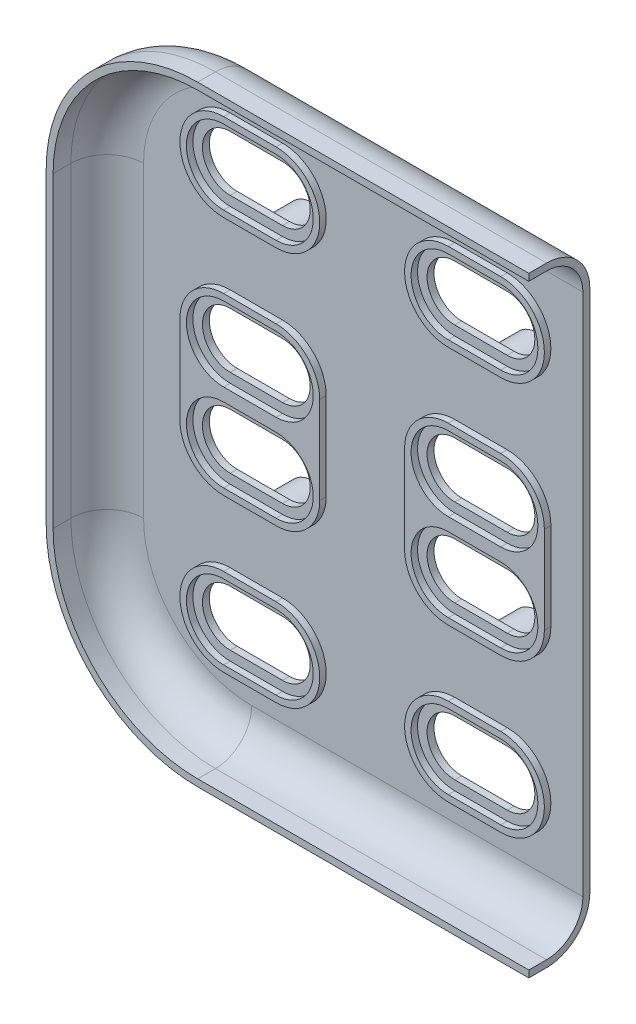
SolidWorks part; units mm, degrees
ref_plane "Front Plane" through (0, 0, 0) normal (0, 0, 1) x (1, 0, 0)
ref_plane "Top Plane" through (0, 0, 0) normal (0, 1, 0) x (1, 0, 0)
ref_plane "Right Plane" through (0, 0, 0) normal (1, 0, 0) x (0, 0, -1)
sketch "Sketch1" plane through (0, 0, 0) normal (0, 0, 1) x (1, 0, 0)
  line L1 (-15.748, 16.51) -> (15.748, 16.51)
  line L2 (-15.748, 16.51) -> (-15.748, -16.51)
  line L3 (-15.748, -16.51) -> (15.748, -16.51)
  line L4 (15.748, 16.51) -> (15.748, -16.51)
  dimension "D1" = 31.496
  dimension "D2" = 15.748
  dimension "D3" = 33.02
  dimension "D4" = 16.51
extrude "Boss-Extrude1" add sketch "Sketch1" along normal blind 6.9088
shell "Shell1" thickness 0.3048 removed face at (0, 16.51, 3.4544)
sketch "Sketch2" plane through (0, 0, 0) normal (1, 0, 0) x (0, 0, -1)
  line L0 (-6.9088, 16.51) -> (0, 16.51) construction
  line L1 (-3.4544, 16.51) -> (0.4052, 16.51)
  line L2 (-3.4544, 16.51) -> (-3.4544, -16.733)
  line L3 (-3.4544, -16.733) -> (0.4052, -16.733)
  line L4 (0.4052, 16.51) -> (0.4052, -16.733)
extrude "Cut-Extrude1" cut sketch "Sketch2" against normal mid plane 34.5948
sketch "Sketch3" plane through (0, 0, 6.9088) normal (0, 0, 1) x (1, 0, 0)
  line L0 (-8.128, 12.954) -> (-5.0546, 12.954) construction
  line L1 (-8.128, 14.5796) -> (-5.0546, 14.5796)
  line L2 (-8.128, 11.3284) -> (-5.0546, 11.3284)
  line L3 (-15.748, -6.985) -> (-15.748, 16.51) construction
  line L4 (15.748, 16.51) -> (-15.748, 16.51) construction
  arc A0 (-8.128, 14.5796) -> (-8.128, 11.3284) centre (-8.128, 12.954) ccw
  arc A1 (-5.0546, 11.3284) -> (-5.0546, 14.5796) centre (-5.0546, 12.954) ccw
  point P2 (-6.5913, 12.954)
  dimension "D1" = 1.6256
  dimension "D2" = 3.0734
  dimension "D3" = 7.62
  dimension "D4" = 3.556
extrude "Cut-Extrude2" cut sketch "Sketch3" against normal through all
sketch "Sketch4" plane through (0, 0, 6.9088) normal (0, 0, 1) x (1, 0, 0)
  line L0 (-15.748, -6.985) -> (-15.748, 16.51) construction
  circle A0 centre (-6.6167, 8.4582) radius 1.143
  arc A1 (-5.0546, 11.3284) -> (-5.0546, 14.5796) centre (-5.0546, 12.954) ccw construction
  dimension "D1" = 2.286
  dimension "D2" = 4.4958
  dimension "D3" = 9.1313
extrude "Cut-Extrude3" cut sketch "Sketch4" against normal through all
sketch "Sketch5" plane through (0, 0, 6.9088) normal (0, 0, 1) x (1, 0, 0)
  line L0 (-8.128, 3.9624) -> (-5.0546, 3.9624) construction
  line L1 (-8.128, 5.588) -> (-5.0546, 5.588)
  line L2 (-8.128, 2.3368) -> (-5.0546, 2.3368)
  line L3 (-8.128, -1.1684) -> (-5.0546, -1.1684) construction
  line L4 (-8.128, 0.4572) -> (-5.0546, 0.4572)
  line L5 (-8.128, -2.794) -> (-5.0546, -2.794)
  line L6 (-15.748, -6.985) -> (-15.748, 16.51) construction
  line L7 (-8.128, -10.16) -> (-5.0546, -10.16) construction
  line L8 (-8.128, -8.5344) -> (-5.0546, -8.5344)
  line L9 (-8.128, -11.7856) -> (-5.0546, -11.7856)
  arc A0 (-8.128, 5.588) -> (-8.128, 2.3368) centre (-8.128, 3.9624) ccw
  arc A1 (-5.0546, 2.3368) -> (-5.0546, 5.588) centre (-5.0546, 3.9624) ccw
  arc A2 (-8.128, 0.4572) -> (-8.128, -2.794) centre (-8.128, -1.1684) ccw
  arc A3 (-5.0546, -2.794) -> (-5.0546, 0.4572) centre (-5.0546, -1.1684) ccw
  circle A4 centre (-6.6167, 8.4582) radius 1.143 construction
  circle A5 centre (-6.5913, -5.6642) radius 1.143
  arc A6 (-8.128, -8.5344) -> (-8.128, -11.7856) centre (-8.128, -10.16) ccw
  arc A7 (-5.0546, -11.7856) -> (-5.0546, -8.5344) centre (-5.0546, -10.16) ccw
  point P2 (-6.5913, 3.9624)
  point P7 (-6.5913, -1.1684)
  point P22 (-6.5913, -10.16)
  dimension "D1" = 1.6256
  dimension "D2" = 1.6256
  dimension "D4" = 3.0734
  dimension "D9" = 2.286
  dimension "D11" = 1.6256
  dimension "D3" = 4.4958
  dimension "D5" = 3.0734
  dimension "D6" = 5.1308
  dimension "D7" = 7.62
  dimension "D8" = 7.62
  dimension "D10" = 4.4958
  dimension "D12" = 8.9916
  dimension "D13" = 7.62
  dimension "D14" = 3.0734
extrude "Cut-Extrude4" cut sketch "Sketch5" against normal blind 2.54
mirror "Mirror1" about plane through (0, 0, 0) normal (1, 0, 0) of "Cut-Extrude4", "Cut-Extrude3", "Cut-Extrude2"
sketch "Sketch6" plane through (0, 0, 3.4544) normal (0, 0, -1) x (-1, 0, 0)
  line L1 (-15.748, -16.51) -> (15.748, -16.51)
  line L2 (-15.748, -16.51) -> (-15.748, 16.51)
  line L3 (-15.748, 16.51) -> (15.748, 16.51)
  line L4 (15.748, -16.51) -> (15.748, 16.51)
extrude "Cut-Extrude5" cut sketch "Sketch6" against normal up to surface (3.1496 mm away) up to face at (6.5913, -1.1684, 6.604)
sketch "Sketch7" plane through (0, 0, 6.604) normal (0, 0, -1) x (-1, 0, 0)
  line L1 (-15.748, 16.51) -> (15.748, 16.51)
  line L2 (-15.748, 16.51) -> (-15.748, 19.304)
  line L3 (-15.748, 19.304) -> (15.748, 19.304)
  line L4 (15.748, 16.51) -> (15.748, 19.304)
  dimension "D1" = 2.794
extrude "Boss-Extrude2" add sketch "Sketch7" against normal up to surface (0.3048 mm away) up to face at (6.5913, -10.16, 6.9088)
fillet "Fillet1" radius 8.89 2 edges at (-15.748, -16.51, 6.7564) (-15.748, 19.304, 6.7564)
sketch "Sketch9" plane through (0, 0, 6.9088) normal (0, 0, 1) x (1, 0, 0)
  line L0 (-6.858, -16.51) -> (15.748, -16.51) construction
  line L1 (-15.748, 10.414) -> (-15.748, -7.62) construction
  line L2 (-6.858, 19.304) -> (15.748, 19.304) construction
  line L3 (15.748, -16.51) -> (15.748, 19.304) construction
  line L4 (-6.858, -16.51) -> (15.748, -16.51)
  line L5 (-15.748, 10.414) -> (-15.748, -7.62)
  line L6 (-6.858, 19.304) -> (15.748, 19.304)
  line L7 (15.748, -16.51) -> (15.748, 19.304)
  arc A0 (-15.748, -7.62) -> (-6.858, -16.51) centre (-6.858, -7.62) ccw construction
  arc A1 (-6.858, 19.304) -> (-15.748, 10.414) centre (-6.858, 10.414) ccw construction
  arc A2 (-15.748, -7.62) -> (-6.858, -16.51) centre (-6.858, -7.62) ccw
  arc A3 (-6.858, 19.304) -> (-15.748, 10.414) centre (-6.858, 10.414) ccw
extrude "Boss-Extrude4" add sketch "Sketch9" along normal blind 3.0226
fillet "Fillet2" radius 2.54 5 edges at (4.445, -16.51, 6.604) (-13.1442, -13.9062, 6.604) (-15.748, 1.397, 6.604) (-13.1442, 16.7002, 6.604) (4.445, 19.304, 6.604)
shell "Shell3" thickness 0.4064 removed face at (-2.8997, 1.397, 9.9314)
sketch "Sketch10" plane through (15.3416, 0, 0) normal (-1, 0, 0) x (0, 0, 1)
  line L0 (9.9314, 18.8976) -> (9.144, 18.8976) construction
  line L1 (9.9314, -16.1036) -> (9.9314, 18.8976) construction
  line L2 (9.9314, -16.1036) -> (9.144, -16.1036) construction
  line L3 (7.0104, 16.764) -> (7.0104, -13.97) construction
  line L4 (9.9314, 18.8976) -> (9.144, 18.8976)
  line L5 (9.9314, -16.1036) -> (9.9314, 18.8976)
  line L6 (9.9314, -16.1036) -> (9.144, -16.1036)
  line L7 (7.0104, 16.764) -> (7.0104, -13.97)
  arc A0 (7.0104, -13.97) -> (9.144, -16.1036) centre (9.144, -13.97) ccw construction
  arc A1 (9.144, 18.8976) -> (7.0104, 16.764) centre (9.144, 16.764) ccw construction
  arc A2 (7.0104, -13.97) -> (9.144, -16.1036) centre (9.144, -13.97) ccw
  arc A3 (9.144, 18.8976) -> (7.0104, 16.764) centre (9.144, 16.764) ccw
extrude "Cut-Extrude6" cut sketch "Sketch10" against normal blind 3.0226
sketch "Sketch12" plane through (0, 0, 6.604) normal (0, 0, -1) x (-1, 0, 0)
  line L0 (-8.128, -11.7856) -> (-5.0546, -11.7856) construction
  line L1 (-5.0546, -8.5344) -> (-8.128, -8.5344) construction
  line L2 (-8.128, -2.794) -> (-5.0546, -2.794) construction
  line L3 (-5.0546, 0.4572) -> (-8.128, 0.4572) construction
  line L4 (-8.128, 2.3368) -> (-5.0546, 2.3368) construction
  line L5 (-5.0546, 5.588) -> (-8.128, 5.588) construction
  line L6 (-8.128, 11.3284) -> (-5.0546, 11.3284) construction
  line L7 (-5.0546, 14.5796) -> (-8.128, 14.5796) construction
  line L8 (-8.128, -11.7856) -> (-5.0546, -11.7856)
  line L9 (-5.0546, -8.5344) -> (-8.128, -8.5344)
  line L10 (-8.128, -2.794) -> (-5.0546, -2.794)
  line L11 (-5.0546, 0.4572) -> (-8.128, 0.4572)
  line L12 (-8.128, 2.3368) -> (-5.0546, 2.3368)
  line L13 (-5.0546, 5.588) -> (-8.128, 5.588)
  line L14 (-8.128, 11.3284) -> (-5.0546, 11.3284)
  line L15 (-5.0546, 14.5796) -> (-8.128, 14.5796)
  arc A0 (-8.128, -8.5344) -> (-8.128, -11.7856) centre (-8.128, -10.16) ccw construction
  arc A1 (-5.0546, -11.7856) -> (-5.0546, -8.5344) centre (-5.0546, -10.16) ccw construction
  circle A2 centre (-6.5913, -5.6642) radius 1.143 construction
  arc A3 (-8.128, 0.4572) -> (-8.128, -2.794) centre (-8.128, -1.1684) ccw construction
  arc A4 (-5.0546, -2.794) -> (-5.0546, 0.4572) centre (-5.0546, -1.1684) ccw construction
  arc A5 (-8.128, 5.588) -> (-8.128, 2.3368) centre (-8.128, 3.9624) ccw construction
  arc A6 (-5.0546, 2.3368) -> (-5.0546, 5.588) centre (-5.0546, 3.9624) ccw construction
  circle A7 centre (-6.6167, 8.4582) radius 1.143 construction
  arc A8 (-8.128, 14.5796) -> (-8.128, 11.3284) centre (-8.128, 12.954) ccw construction
  arc A9 (-5.0546, 11.3284) -> (-5.0546, 14.5796) centre (-5.0546, 12.954) ccw construction
  arc A10 (-8.128, -8.5344) -> (-8.128, -11.7856) centre (-8.128, -10.16) ccw
  arc A11 (-5.0546, -11.7856) -> (-5.0546, -8.5344) centre (-5.0546, -10.16) ccw
  circle A12 centre (-6.5913, -5.6642) radius 1.143
  arc A13 (-8.128, 0.4572) -> (-8.128, -2.794) centre (-8.128, -1.1684) ccw
  arc A14 (-5.0546, -2.794) -> (-5.0546, 0.4572) centre (-5.0546, -1.1684) ccw
  arc A15 (-8.128, 5.588) -> (-8.128, 2.3368) centre (-8.128, 3.9624) ccw
  arc A16 (-5.0546, 2.3368) -> (-5.0546, 5.588) centre (-5.0546, 3.9624) ccw
  circle A17 centre (-6.6167, 8.4582) radius 1.143
  arc A18 (-8.128, 14.5796) -> (-8.128, 11.3284) centre (-8.128, 12.954) ccw
  arc A19 (-5.0546, 11.3284) -> (-5.0546, 14.5796) centre (-5.0546, 12.954) ccw
extrude "Cut-Extrude7" cut sketch "Sketch12" against normal blind 3.0226
mirror "Mirror2" about plane through (0, 0, 0) normal (1, 0, 0) of "Mirror1"
sketch "Sketch14" plane through (0, 0, 6.604) normal (0, 0, -1) x (-1, 0, 0)
  line L0 (5.0546, 14.5796) -> (8.128, 14.5796) construction
  line L1 (8.128, 11.3284) -> (5.0546, 11.3284) construction
  line L2 (5.0546, 5.588) -> (8.128, 5.588) construction
  line L3 (8.128, 2.3368) -> (5.0546, 2.3368) construction
  line L4 (5.0546, 0.4572) -> (8.128, 0.4572) construction
  line L5 (8.128, -2.794) -> (5.0546, -2.794) construction
  line L6 (8.128, -11.7856) -> (5.0546, -11.7856) construction
  line L7 (5.0546, -8.5344) -> (8.128, -8.5344) construction
  line L8 (5.0546, 14.5796) -> (8.128, 14.5796)
  line L9 (8.128, 11.3284) -> (5.0546, 11.3284)
  line L10 (5.0546, 5.588) -> (8.128, 5.588)
  line L11 (8.128, 2.3368) -> (5.0546, 2.3368)
  line L12 (5.0546, 0.4572) -> (8.128, 0.4572)
  line L13 (8.128, -2.794) -> (5.0546, -2.794)
  line L14 (8.128, -11.7856) -> (5.0546, -11.7856)
  line L15 (5.0546, -8.5344) -> (8.128, -8.5344)
  arc A0 (8.128, 11.3284) -> (8.128, 14.5796) centre (8.128, 12.954) ccw construction
  arc A1 (5.0546, 14.5796) -> (5.0546, 11.3284) centre (5.0546, 12.954) ccw construction
  circle A2 centre (6.6167, 8.4582) radius 1.143 construction
  arc A3 (8.128, 2.3368) -> (8.128, 5.588) centre (8.128, 3.9624) ccw construction
  arc A4 (5.0546, 5.588) -> (5.0546, 2.3368) centre (5.0546, 3.9624) ccw construction
  arc A5 (8.128, -2.794) -> (8.128, 0.4572) centre (8.128, -1.1684) ccw construction
  arc A6 (5.0546, 0.4572) -> (5.0546, -2.794) centre (5.0546, -1.1684) ccw construction
  circle A7 centre (6.5913, -5.6642) radius 1.143 construction
  arc A8 (8.128, -11.7856) -> (8.128, -8.5344) centre (8.128, -10.16) ccw construction
  arc A9 (5.0546, -8.5344) -> (5.0546, -11.7856) centre (5.0546, -10.16) ccw construction
  arc A10 (8.128, 11.3284) -> (8.128, 14.5796) centre (8.128, 12.954) ccw
  arc A11 (5.0546, 14.5796) -> (5.0546, 11.3284) centre (5.0546, 12.954) ccw
  circle A12 centre (6.6167, 8.4582) radius 1.143
  arc A13 (8.128, 2.3368) -> (8.128, 5.588) centre (8.128, 3.9624) ccw
  arc A14 (5.0546, 5.588) -> (5.0546, 2.3368) centre (5.0546, 3.9624) ccw
  arc A15 (8.128, -2.794) -> (8.128, 0.4572) centre (8.128, -1.1684) ccw
  arc A16 (5.0546, 0.4572) -> (5.0546, -2.794) centre (5.0546, -1.1684) ccw
  circle A17 centre (6.5913, -5.6642) radius 1.143
  arc A18 (8.128, -11.7856) -> (8.128, -8.5344) centre (8.128, -10.16) ccw
  arc A19 (5.0546, -8.5344) -> (5.0546, -11.7856) centre (5.0546, -10.16) ccw
extrude "Cut-Extrude8" cut sketch "Sketch14" against normal blind 3.0226
sketch "Sketch15" plane through (0, 0, 7.3152) normal (0, 0, 1) x (1, 0, 0)
  line L1 (-10.354, -12.4898) -> (11.5088, -12.4898)
  line L2 (-10.354, -12.4898) -> (-10.354, 15.2063)
  line L3 (-10.354, 15.2063) -> (11.5088, 15.2063)
  line L4 (11.5088, -12.4898) -> (11.5088, 15.2063)
extrude "Cut-Extrude9" cut sketch "Sketch15" against normal up to surface (0.3048 mm away) up to face at (6.5913, -1.1684, 7.0104)
sketch "Sketch16" plane through (0, 0, 6.604) normal (0, 0, -1) x (-1, 0, 0)
  line L0 (6.858, -16.51) -> (-15.748, -16.51) construction
  line L1 (-15.748, 19.304) -> (-12.573, 19.304)
  line L2 (-15.748, 19.304) -> (-15.748, -16.51)
  line L3 (-15.748, -16.51) -> (-12.573, -16.51)
  line L4 (-12.573, 19.304) -> (-12.573, -16.51)
  dimension "D1" = 3.175
extrude "Cut-Extrude10" cut sketch "Sketch16" against normal through all
sketch "Sketch17" plane through (0, 0, 9.9314) normal (0, 0, 1) x (1, 0, 0)
  line L0 (-6.858, -16.51) -> (12.573, -16.51) construction
  line L1 (-6.858, -16.1036) -> (12.573, -16.1036) construction
  line L2 (-15.3416, 10.414) -> (-15.3416, -7.62) construction
  line L3 (-15.748, 10.414) -> (-15.748, -7.62) construction
  line L4 (12.573, 18.8976) -> (-6.858, 18.8976) construction
  line L5 (12.573, 19.304) -> (-6.858, 19.304) construction
  line L6 (-6.858, -16.51) -> (12.573, -16.51)
  line L7 (-6.858, -16.1036) -> (12.573, -16.1036)
  line L8 (-15.3416, 10.414) -> (-15.3416, -7.62)
  line L9 (-15.748, 10.414) -> (-15.748, -7.62)
  line L10 (12.573, 18.8976) -> (-6.858, 18.8976)
  line L11 (12.573, 19.304) -> (-6.858, 19.304)
  line L12 (12.573, -16.1036) -> (12.573, -16.51)
  line L13 (12.573, 19.304) -> (12.573, 18.8976)
  arc A0 (-15.748, -7.62) -> (-6.858, -16.51) centre (-6.858, -7.62) ccw construction
  arc A1 (-15.3416, -7.62) -> (-6.858, -16.1036) centre (-6.858, -7.62) ccw construction
  arc A2 (-6.858, 19.304) -> (-15.748, 10.414) centre (-6.858, 10.414) ccw construction
  arc A3 (-6.858, 18.8976) -> (-15.3416, 10.414) centre (-6.858, 10.414) ccw construction
  arc A4 (-15.748, -7.62) -> (-6.858, -16.51) centre (-6.858, -7.62) ccw
  arc A5 (-15.3416, -7.62) -> (-6.858, -16.1036) centre (-6.858, -7.62) ccw
  arc A6 (-6.858, 19.304) -> (-15.748, 10.414) centre (-6.858, 10.414) ccw
  arc A7 (-6.858, 18.8976) -> (-15.3416, 10.414) centre (-6.858, 10.414) ccw
extrude "Boss-Extrude5" add sketch "Sketch17" along normal blind 0.254
sketch "Sketch21" plane through (0, 0, 7.0104) normal (0, 0, 1) x (1, 0, 0)
  line L6 (-5.0546, -7.5946) -> (-8.128, -7.5946)
  line L7 (-8.128, -12.7254) -> (-5.0546, -12.7254)
  line L8 (-8.128, -12.3444) -> (-5.0546, -12.3444)
  line L9 (-5.0546, -7.9756) -> (-8.128, -7.9756)
  line L10 (-8.128, -12.3444) -> (-5.0546, -12.3444)
  line L11 (-5.0546, -7.9756) -> (-8.128, -7.9756)
  arc A4 (-8.128, -7.5946) -> (-8.128, -12.7254) centre (-8.128, -10.16) ccw
  arc A5 (-5.0546, -12.7254) -> (-5.0546, -7.5946) centre (-5.0546, -10.16) ccw
  arc A6 (-5.0546, -12.3444) -> (-5.0546, -7.9756) centre (-5.0546, -10.16) ccw
  arc A7 (-8.128, -7.9756) -> (-8.128, -12.3444) centre (-8.128, -10.16) ccw
  arc A8 (-5.0546, -12.3444) -> (-5.0546, -7.9756) centre (-5.0546, -10.16) ccw
  arc A9 (-8.128, -7.9756) -> (-8.128, -12.3444) centre (-8.128, -10.16) ccw
  dimension "D1" = 0.5588
  dimension "D2" = 0.381
extrude "Boss-Extrude8" add sketch "Sketch21" along normal blind 0.381
sketch "Sketch23" plane through (0, 0, 7.0104) normal (0, 0, 1) x (1, 0, 0)
  line L6 (-5.0546, 6.5278) -> (-8.128, 6.5278)
  line L8 (-8.128, 1.778) -> (-5.0546, 1.778)
  line L9 (-5.0546, 6.1468) -> (-8.128, 6.1468)
  line L10 (-8.128, 1.778) -> (-5.0546, 1.778)
  line L11 (-5.0546, 6.1468) -> (-8.128, 6.1468)
  line L19 (-8.128, -3.7338) -> (-5.0546, -3.7338)
  line L20 (-8.128, -3.3528) -> (-5.0546, -3.3528)
  line L21 (-5.0546, 1.016) -> (-8.128, 1.016)
  line L22 (-8.128, -3.3528) -> (-5.0546, -3.3528)
  line L23 (-5.0546, 1.016) -> (-8.128, 1.016)
  line L24 (-5.0546, 1.397) -> (-8.128, 1.397) construction
  line L25 (-8.128, 1.397) -> (-5.0546, 1.397) construction
  line L26 (-10.6934, 3.9624) -> (-10.6934, -1.1684)
  line L27 (-2.4892, 3.9624) -> (-2.4892, -1.1684)
  arc A4 (-8.128, 6.5278) -> (-10.6934, 3.9624) centre (-8.128, 3.9624) ccw
  arc A5 (-2.4892, 3.9624) -> (-5.0546, 6.5278) centre (-5.0546, 3.9624) ccw
  arc A6 (-5.0546, 1.778) -> (-5.0546, 6.1468) centre (-5.0546, 3.9624) ccw
  arc A7 (-8.128, 6.1468) -> (-8.128, 1.778) centre (-8.128, 3.9624) ccw
  arc A8 (-5.0546, 1.778) -> (-5.0546, 6.1468) centre (-5.0546, 3.9624) ccw
  arc A9 (-8.128, 6.1468) -> (-8.128, 1.778) centre (-8.128, 3.9624) ccw
  arc A14 (-10.6934, -1.1684) -> (-8.128, -3.7338) centre (-8.128, -1.1684) ccw
  arc A15 (-5.0546, -3.7338) -> (-2.4892, -1.1684) centre (-5.0546, -1.1684) ccw
  arc A16 (-5.0546, -3.3528) -> (-5.0546, 1.016) centre (-5.0546, -1.1684) ccw
  arc A17 (-8.128, 1.016) -> (-8.128, -3.3528) centre (-8.128, -1.1684) ccw
  arc A18 (-5.0546, -3.3528) -> (-5.0546, 1.016) centre (-5.0546, -1.1684) ccw
  arc A19 (-8.128, 1.016) -> (-8.128, -3.3528) centre (-8.128, -1.1684) ccw
  arc A20 (-8.128, 1.397) -> (-8.128, -3.7338) centre (-8.128, -1.1684) ccw construction
  arc A21 (-8.128, 6.5278) -> (-8.128, 1.397) centre (-8.128, 3.9624) ccw construction
  arc A22 (-5.0546, 1.397) -> (-5.0546, 6.5278) centre (-5.0546, 3.9624) ccw construction
  arc A23 (-5.0546, -3.7338) -> (-5.0546, 1.397) centre (-5.0546, -1.1684) ccw construction
  dimension "D1" = 0.5588
  dimension "D2" = 0.381
  dimension "D3" = 0.5588
  dimension "D4" = 0.381
extrude "Boss-Extrude9" add sketch "Sketch23" along normal blind 0.381
mirror "Mirror3" about plane through (0, 0, 0) normal (1, 0, 0) of "Boss-Extrude8", "Boss-Extrude9"
sketch "Sketch24" plane through (0, 0, 7.0104) normal (0, 0, 1) x (1, 0, 0)
  line L6 (-5.0546, 15.5194) -> (-8.128, 15.5194)
  line L7 (-8.128, 10.3886) -> (-5.0546, 10.3886)
  line L8 (-8.128, 10.7696) -> (-5.0546, 10.7696)
  line L9 (-5.0546, 15.1384) -> (-8.128, 15.1384)
  line L10 (-8.128, 10.7696) -> (-5.0546, 10.7696)
  line L11 (-5.0546, 15.1384) -> (-8.128, 15.1384)
  arc A4 (-8.128, 15.5194) -> (-8.128, 10.3886) centre (-8.128, 12.954) ccw
  arc A5 (-5.0546, 10.3886) -> (-5.0546, 15.5194) centre (-5.0546, 12.954) ccw
  arc A6 (-5.0546, 10.7696) -> (-5.0546, 15.1384) centre (-5.0546, 12.954) ccw
  arc A7 (-8.128, 15.1384) -> (-8.128, 10.7696) centre (-8.128, 12.954) ccw
  arc A8 (-5.0546, 10.7696) -> (-5.0546, 15.1384) centre (-5.0546, 12.954) ccw
  arc A9 (-8.128, 15.1384) -> (-8.128, 10.7696) centre (-8.128, 12.954) ccw
  dimension "D1" = 0.5588
  dimension "D2" = 0.381
extrude "Boss-Extrude10" add sketch "Sketch24" along normal blind 0.381
mirror "Mirror5" about plane through (0, 0, 0) normal (1, 0, 0) of "Boss-Extrude10"
sketch "Sketch25" plane through (0, 0, 6.604) normal (0, 0, -1) x (-1, 0, 0)
  circle A0 centre (-6.6167, 8.4582) radius 1.5875
  circle A1 centre (-6.5913, -5.6642) radius 1.5875
  circle A2 centre (6.6167, 8.4582) radius 1.5875
  circle A3 centre (6.5913, -5.6642) radius 1.5875
  circle A4 centre (-6.6167, 8.4582) radius 0.8636
  circle A5 centre (6.6167, 8.4582) radius 0.8636
  circle A6 centre (-6.5913, -5.6642) radius 0.8636
  circle A7 centre (6.5913, -5.6642) radius 0.8636
  dimension "D1" = 3.175
  dimension "D2" = 3.175
  dimension "D3" = 3.175
  dimension "D4" = 3.175
  dimension "D5" = 1.7272
  dimension "D6" = 1.7272
  dimension "D7" = 1.7272
  dimension "D8" = 1.7272
extrude "Boss-Extrude11" add sketch "Sketch25" along normal blind 2.921
chamfer "Chamfer1" distance 0.254 angle 45 4 edges at (-7.4549, -5.6642, 3.683) (5.7277, -5.6642, 3.683) (-7.4803, 8.4582, 3.683) (5.7531, 8.4582, 3.683)
sketch "Sketch26" plane through (0, 0, 6.604) normal (0, 0, 1) x (1, 0, 0)
  circle A0 centre (-6.5913, -5.6642) radius 1.143 construction
  circle A1 centre (6.5913, -5.6642) radius 1.143 construction
  circle A2 centre (6.6167, 8.4582) radius 1.143 construction
  circle A3 centre (-6.6167, 8.4582) radius 1.143 construction
  circle A4 centre (-6.5913, -5.6642) radius 1.143
  circle A5 centre (6.5913, -5.6642) radius 1.143
  circle A6 centre (6.6167, 8.4582) radius 1.143
  circle A7 centre (-6.6167, 8.4582) radius 1.143
extrude "Boss-Extrude12" add sketch "Sketch26" along normal up to surface (0.4064 mm away) up to face at (6.5913, 12.954, 7.0104)
